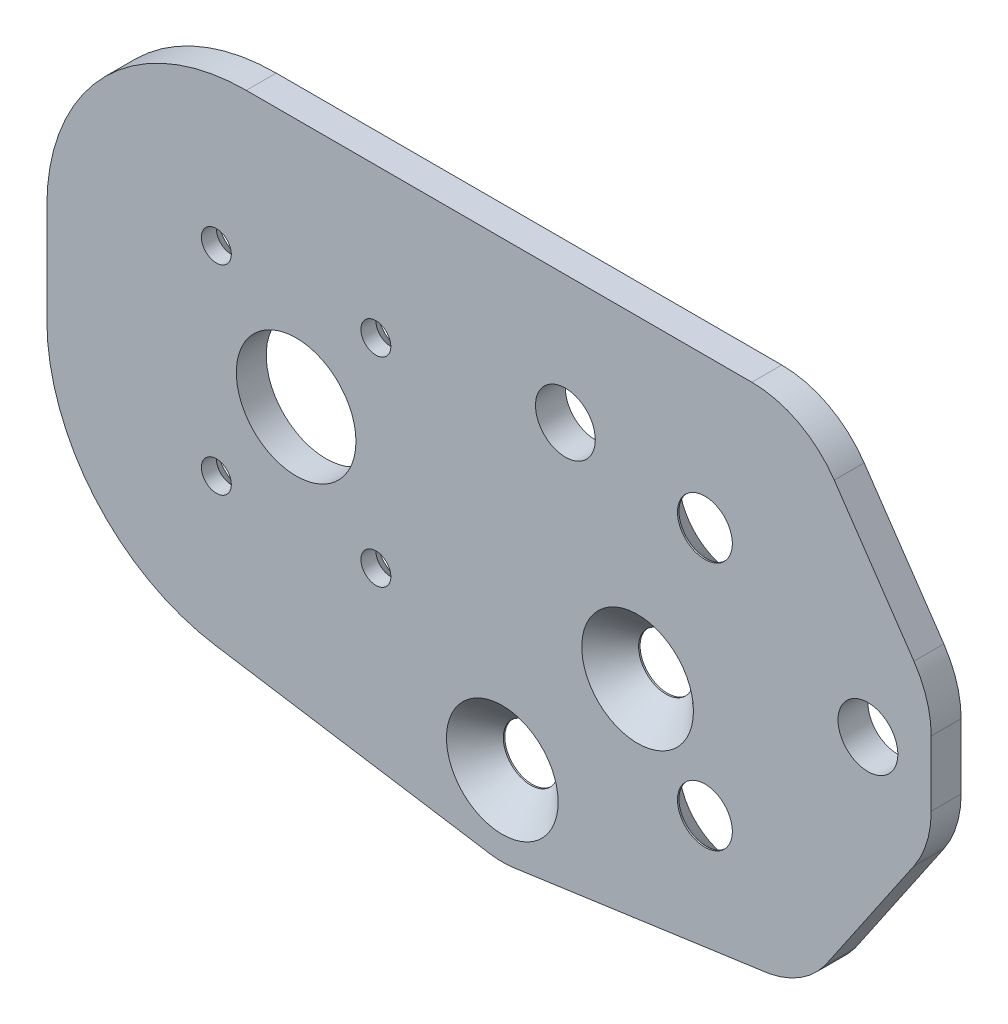
SolidWorks part; units mm, degrees
material "Gerais  - 6061-T6"
ref_plane "Plano frontal" through (0, 0, 0) normal (0, 0, 1) x (1, 0, 0)
ref_plane "Plano superior" through (0, 0, 0) normal (0, 1, 0) x (1, 0, 0)
ref_plane "Plano direito" through (0, 0, 0) normal (1, 0, 0) x (0, 0, -1)
sketch "Esboço1" plane through (0, 0, 0) normal (0, 0, 1) x (1, 0, 0)
  line L0 (56, 50) -> (56, 0) construction
  line L1 (0, 0) -> (76, 0)
  line L2 (0, 0) -> (0, 50)
  line L3 (0, 50) -> (76, 50)
  line L4 (76, 0) -> (76, 50)
  line L5 (66, 50) -> (66, 18.5) construction
  line L6 (65.25, 50) -> (65.25, 18.5) construction
  line L7 (59.25, 12.5) -> (25, 12.5) construction
  circle A0 centre (25, 25) radius 16 construction
  circle A1 centre (59.25, 18.5) radius 9.75 construction
  circle A2 centre (59.25, 18.5) radius 6 construction
  circle A3 centre (25, 25) radius 12.5 construction
  circle A4 centre (59.25, 18.5) radius 2.5
  circle A5 centre (25, 25) radius 6
  circle A6 centre (17, 38.8564) radius 1.5 construction
  circle A7 centre (33, 38.8564) radius 1.5 construction
  circle A8 centre (41, 25) radius 1.5 construction
  circle A9 centre (33, 11.1436) radius 1.5 construction
  circle A10 centre (17, 11.1436) radius 1.5 construction
  circle A11 centre (9, 25) radius 1.5 construction
  point P7 (41, 25)
  point P36 (25, 25)
  dimension "D1" = 32
  dimension "D5" = 12
  dimension "D6" = 19.5
  dimension "D9" = 25
  dimension "D10" = 5
  dimension "D13" = 12
  dimension "D14" = 3
  dimension "D2" = 25
  dimension "D3" = 35
  dimension "D4" = 20
  dimension "D7" = 0.75
  dimension "D8" = 10
  dimension "D11" = 25
  dimension "D12" = 50
  dimension "D15" = 6
extrude "Ressalto-extrusão1" add sketch "Esboço1" along normal blind 3
sketch "Esboço2" plane through (0, 0, 3) normal (0, 0, 1) x (1, 0, 0)
  line L0 (66, 50) -> (66, 0) construction
  line L1 (76, 50) -> (0, 50) construction
  line L2 (0, 0) -> (76, 0) construction
  line L3 (76, 0) -> (76, 50) construction
  circle A0 centre (66, 35) radius 2.5
  circle A1 centre (66, 10) radius 2.5
  dimension "D2" = 5
  dimension "D3" = 5
  dimension "D1" = 10
  dimension "D4" = 10
  dimension "D5" = 15
extrude "Corte-extrusão1" cut sketch "Esboço2" against normal blind 3
fillet "Filete1" radius 20 2 edges at (0, 0, 1.5) (0, 50, 1.5)
sketch "Esboço3" plane through (0, 0, 3) normal (0, 0, 1) x (1, 0, 0)
  line L1 (17, 15) -> (33, 15) construction
  line L2 (17, 15) -> (17, 35) construction
  line L3 (17, 35) -> (33, 35) construction
  line L4 (33, 15) -> (33, 35) construction
  line L5 (17, 15) -> (33, 35) construction
  line L6 (17, 35) -> (33, 15) construction
  circle A0 centre (33, 35) radius 1.5
  circle A1 centre (33, 15) radius 1.5
  circle A2 centre (17, 15) radius 1.5
  circle A3 centre (17, 35) radius 1.5
  point P0 (25, 25)
  dimension "D3" = 3
  dimension "D1" = 20
  dimension "D2" = 16
extrude "Corte-extrusão2" cut sketch "Esboço3" against normal through all
sketch "Esboço4" plane through (0, 0, 3) normal (0, 0, 1) x (1, 0, 0)
  line L0 (76, 50) -> (20, 50) construction
  line L1 (55.3323, 43.65) -> (51.6662, 50) construction
  line L2 (51.6662, 50) -> (44.3338, 50) construction
  line L3 (44.3338, 50) -> (40.6677, 43.65) construction
  line L4 (40.6677, 43.65) -> (44.3338, 37.3) construction
  line L5 (44.3338, 37.3) -> (51.6662, 37.3) construction
  line L6 (51.6662, 37.3) -> (55.3323, 43.65) construction
  line L7 (76, 0) -> (76, 50) construction
  line L8 (76, 0) -> (76, 50) construction
  line L9 (49.1263, -2.6618) -> (53.0059, 3.5567) construction
  line L10 (53.0059, 3.5567) -> (49.5604, 10.0258) construction
  line L11 (49.5604, 10.0258) -> (42.2352, 10.2764) construction
  line L12 (42.2352, 10.2764) -> (38.3556, 4.0579) construction
  line L13 (38.3556, 4.0579) -> (41.8011, -2.4112) construction
  line L14 (41.8011, -2.4112) -> (49.1263, -2.6618) construction
  line L15 (25, 12.5) -> (61.6574, 12.5) construction
  line L17 (48, 43.65) -> (45.6807, 3.8073) construction
  circle A0 centre (48, 43.65) radius 3 construction
  circle A1 centre (48, 43.65) radius 6.35 construction
  circle A2 centre (45.6807, 3.8073) radius 2.5
  circle A3 centre (45.6807, 3.8073) radius 6.35 construction
  arc A4 (17.8926, 14.7172) -> (30.3514, 13.7035) centre (25, 25) ccw construction
  arc A5 (17.8926, 14.7172) -> (30.3514, 13.7035) centre (25, 25) ccw construction
  circle A6 centre (52.0071, 37.1424) radius 3
  circle A7 centre (25, 25) radius 29.6112 construction
  circle A8 centre (59.25, 18.5) radius 2.5 construction
  circle A9 centre (59.25, 18.5) radius 2.5 construction
  point P34 (0, 0)
  point P35 (45.9343, 4.0578)
  dimension "D1" = 12.7
  dimension "D3" = 6
  dimension "D4" = 5
  dimension "D6" = 20
  dimension "D2" = 28
  dimension "D5" = 28
  dimension "D7" = 20
extrude "Corte-extrusão3" cut sketch "Esboço4" against normal through all
sketch "Esboço5" plane through (0, 0, 0) normal (0, 0, -1) x (-1, 0, 0)
  line L0 (-76, 0) -> (-46.7969, -4.1147)
  line L1 (-44.4359, -4.0955) -> (-16.8881, 0.2436)
  line L2 (-20, 0) -> (-76, 0) construction
  line L3 (-20, 0) -> (-76, 0) construction
  line L4 (-20, 0) -> (-76, 0)
  line L5 (-20, 0) -> (-76, 0)
  arc A1 (-46.7969, -4.1147) -> (-44.4359, -4.0955) centre (-45.6807, 3.8073) ccw
  arc A2 (-20, 0) -> (0, 20) centre (-20, 20) ccw construction
  point P1 (-45.6157, -4.1927)
  line M5 (-76, 0) -> (-20, 0)
  arc M6 (-20, 0) -> (0, 20) centre (-20, 20) ccw
  line M11 (-76, 0) -> (-20, 0)
  dimension "D1" = 8
extrude "Ressalto-extrusão2" add sketch "Esboço5" against normal through all contours L0 A1 L1 M6 M5 M11 region at (46.6692, -1.4247, 0)
sketch "Esboço6" plane through (0, 0, 0) normal (0, 0, -1) x (-1, 0, 0)
  line L7 (-86.9656, 16.103) -> (-78.0603, 3.0256)
  line L8 (-72.4733, -0.9805) -> (-50.0089, -7.2259)
  line L9 (-46.1556, -7.2697) -> (-15.0816, 0.6142)
  line L10 (0, 20) -> (0, 30)
  line L11 (-20, 50) -> (-70.7112, 50)
  line L12 (-78.9768, 45.6286) -> (-86.9656, 33.897)
  line L13 (-88.7, 28.2685) -> (-88.7, 21.7315)
  line L14 (-86.9656, 16.103) -> (-78.0603, 3.0256)
  line L15 (-72.4733, -0.9805) -> (-50.0089, -7.2259)
  line L16 (-46.1556, -7.2697) -> (-15.0816, 0.6142)
  line L17 (0, 20) -> (0, 30)
  line L18 (-20, 50) -> (-70.7112, 50)
  line L19 (-78.9768, 45.6286) -> (-86.9656, 33.897)
  line L20 (-88.7, 28.2685) -> (-88.7, 21.7315)
  circle A0 centre (-82.35, 25) radius 3 construction
  circle A1 centre (-82.35, 25) radius 3
  arc A7 (-78.0603, 3.0256) -> (-72.4733, -0.9805) centre (-69.7947, 8.6541) ccw
  arc A8 (-50.0089, -7.2259) -> (-46.1556, -7.2697) centre (-48, 0) ccw
  arc A9 (-15.0816, 0.6142) -> (0, 20) centre (-20, 20) ccw
  arc A10 (0, 30) -> (-20, 50) centre (-20, 30) ccw
  arc A11 (-70.7112, 50) -> (-78.9768, 45.6286) centre (-70.7112, 40) ccw
  arc A12 (-86.9656, 33.897) -> (-88.7, 28.2685) centre (-78.7, 28.2685) ccw
  arc A13 (-88.7, 21.7315) -> (-86.9656, 16.103) centre (-78.7, 21.7315) ccw
  arc A15 (-50.0089, -7.2259) -> (-46.1556, -7.2697) centre (-48, 0) ccw
  arc A16 (-15.0816, 0.6142) -> (0, 20) centre (-20, 20) ccw
  arc A17 (0, 30) -> (-20, 50) centre (-20, 30) ccw
  arc A18 (-70.7112, 50) -> (-78.9768, 45.6286) centre (-70.7112, 40) ccw
  arc A19 (-86.9656, 33.897) -> (-88.7, 28.2685) centre (-78.7, 28.2685) ccw
  arc A20 (-88.7, 21.7315) -> (-86.9656, 16.103) centre (-78.7, 21.7315) ccw
  arc A54 (-78.0603, 3.0256) -> (-72.4733, -0.9805) centre (-69.7947, 8.6541) ccw
  line M16 (-76, 50) -> (-76, 0)
  dimension "D1" = 0
extrude "Ressalto-extrusão3" add sketch "Esboço6" against normal through all contours L20 A20 L14 A54 A18 L19 A19 A1 M16 region at (87.7851, 18.9319, 0)
sketch "Esboço7" plane through (0, 0, 0) normal (0, 0, -1) x (-1, 0, 0)
  line L0 (-76, 0) -> (-46.7969, -4.1147) construction
  line L9 (-76, 0.8122) -> (-76, 0)
  line L10 (-76, 0) -> (-46.7969, -4.1147)
  line L11 (-44.4359, -4.0955) -> (-16.8881, 0.2436)
  line L12 (0, 20) -> (0, 30)
  line L13 (-20, 50) -> (-76, 50)
  line L14 (-20, 50) -> (-76, 50)
  line L15 (-78.9768, 45.6286) -> (-86.9656, 33.897)
  line L16 (-88.7, 28.2685) -> (-88.7, 21.7315)
  line L17 (-86.9656, 16.103) -> (-78.0603, 3.0256)
  line L18 (-76, 0.8122) -> (-76, 0)
  line L19 (-76, 0) -> (-46.7969, -4.1147)
  line L20 (-44.4359, -4.0955) -> (-16.8881, 0.2436)
  line L21 (0, 20) -> (0, 30)
  line L24 (-78.9768, 45.6286) -> (-86.9656, 33.897)
  line L25 (-88.7, 28.2685) -> (-88.7, 21.7315)
  line L26 (-86.9656, 16.103) -> (-78.0603, 3.0256)
  line L28 (-76, 50) -> (-76, 48.487)
  line L29 (-76, 50) -> (-76, 48.487)
  arc A0 (-78.9768, 45.6286) -> (-70.7112, 50) centre (-70.7112, 40) cw
  arc A1 (-78.0603, 3.0256) -> (-72.4472, -0.5006) centre (-70.7403, 8.4472) ccw
  arc A7 (-46.7969, -4.1147) -> (-44.4359, -4.0955) centre (-45.6807, 3.8073) ccw
  arc A8 (-16.8881, 0.2436) -> (0, 20) centre (-20, 20) ccw
  arc A9 (0, 30) -> (-20, 50) centre (-20, 30) ccw
  arc A10 (-76, 48.487) -> (-78.9768, 45.6286) centre (-70.7112, 40) ccw
  arc A11 (-86.9656, 33.897) -> (-88.7, 28.2685) centre (-78.7, 28.2685) ccw
  arc A12 (-88.7, 21.7315) -> (-86.9656, 16.103) centre (-78.7, 21.7315) ccw
  arc A14 (-46.7969, -4.1147) -> (-44.4359, -4.0955) centre (-45.6807, 3.8073) ccw
  arc A15 (-16.8881, 0.2436) -> (0, 20) centre (-20, 20) ccw
  arc A17 (-76, 48.487) -> (-78.9768, 45.6286) centre (-70.7112, 40) ccw
  arc A18 (-86.9656, 33.897) -> (-88.7, 28.2685) centre (-78.7, 28.2685) ccw
  arc A19 (-88.7, 21.7315) -> (-86.9656, 16.103) centre (-78.7, 21.7315) ccw
  arc A22 (-78.0603, 3.0256) -> (-76, 0.8122) centre (-69.7947, 8.6541) ccw
  arc A23 (-78.0603, 3.0256) -> (-76, 0.8122) centre (-69.7947, 8.6541) ccw
  arc A24 (0, 30) -> (-20, 50) centre (-20, 30) ccw
  line M18 (-76, 0.8122) -> (-76, 0)
  line M19 (-76, 0) -> (-46.7969, -4.1147)
  line M26 (-76, 50) -> (-76, 48.487)
  dimension "D1" = 0
extrude "Corte-extrusão4" cut sketch "Esboço7" against normal through all contours A1 M18 M19 | A0 L14 M26 region at (75.2939, 0.3649, 0) region at (74.6987, 49.5527, 0)
chamfer "Chanfro1" distance 1.5 angle 45 4 edges at (18.5, 35, 0) (18.5, 15, 0) (34.5, 15, 0) (34.5, 35, 0)
hole_wizard "Escareado para SFHCS M51" positions "Esboço16" profile "Esboço17" countersink size "M5" standard "Ansi Metric" end condition through all
sketch "Esboço16" plane through (0, 0, 3) normal (0, 0, 1) x (1, 0, 0)
  point P0 (45.6807, 3.8073)
sketch "Esboço17" plane through (45.6807, 3.8073, 3) normal (1, 0, 0) x (0, -1, 0)
  line L0 (0, 0) -> (0, 3)
  line L1 (0, 3) -> (2.75, 3)
  line L2 (2.75, 3) -> (2.75, 2.85)
  line L3 (2.75, 2.85) -> (5.6, 0)
  line L5 (5.6, 0) -> (0, 0)
  line L6 (-2.75, 2.85) -> (-5.6, 0) construction
  line L11 (0, -6.35) -> (0, 107.95) construction
  dimension "Thru Hole Dia." = 5.5
  dimension "Thru Hole Depth" = 3
  dimension "Near C'Sink Dia." = 11.2
  dimension "Near C'Sink Angle" = 90
hole_wizard "Escareado para SFHCS M52" positions "Esboço18" profile "Esboço19" countersink size "M5" standard "Ansi Metric" end condition through all
sketch "Esboço18" plane through (0, 0, 3) normal (0, 0, 1) x (1, 0, 0)
  point P0 (59.25, 18.5)
sketch "Esboço19" plane through (59.25, 18.5, 3) normal (1, 0, 0) x (0, -1, 0)
  line L0 (0, 0) -> (0, 3)
  line L1 (0, 3) -> (2.75, 3)
  line L2 (2.75, 3) -> (2.75, 2.85)
  line L3 (2.75, 2.85) -> (5.6, 0)
  line L5 (5.6, 0) -> (0, 0)
  line L6 (-2.75, 2.85) -> (-5.6, 0) construction
  line L11 (0, -6.35) -> (0, 107.95) construction
  dimension "Thru Hole Dia." = 5.5
  dimension "Thru Hole Depth" = 3
  dimension "Near C'Sink Dia." = 11.2
  dimension "Near C'Sink Angle" = 90
hole_wizard "Escareado para SFHCS M54" positions "Esboço22" profile "Esboço23" countersink size "M5" standard "Ansi Metric" end condition through all
sketch "Esboço22" plane through (0, 0, 0) normal (0, 0, -1) x (-1, 0, 0)
  point P0 (-66, 35)
  point P3 (-66, 10)
sketch "Esboço23" plane through (66, 35, 0) normal (1, 0, 0) x (0, 1, 0)
  line L0 (0, 0) -> (0, 3)
  line L1 (0, 3) -> (2.75, 3)
  line L2 (2.75, 3) -> (2.75, 2.85)
  line L3 (2.75, 2.85) -> (5.6, 0)
  line L5 (5.6, 0) -> (0, 0)
  line L6 (-2.75, 2.85) -> (-5.6, 0) construction
  line L11 (0, -6.35) -> (0, 107.95) construction
  dimension "Thru Hole Dia." = 5.5
  dimension "Thru Hole Depth" = 3
  dimension "Near C'Sink Dia." = 11.2
  dimension "Near C'Sink Angle" = 90
